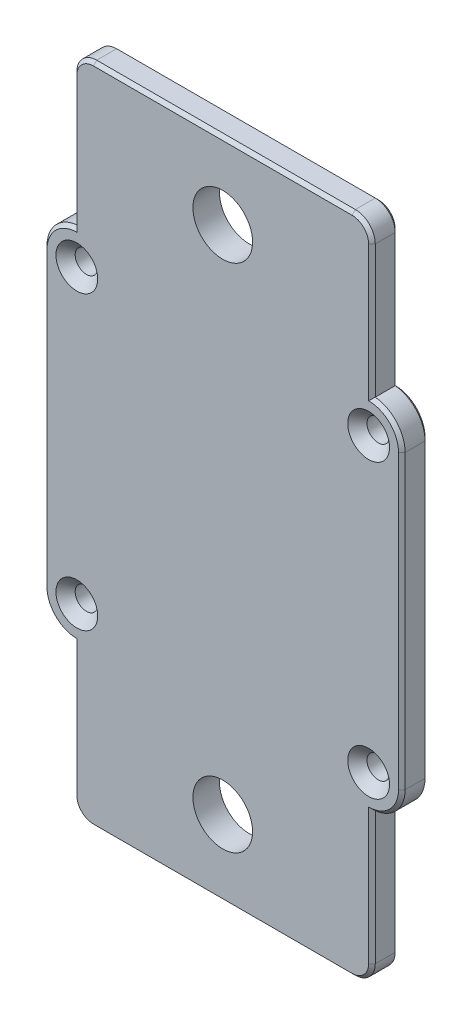
SolidWorks part; units mm, degrees
ref_plane "Plan de face" through (0, 0, 0) normal (0, 0, 1) x (1, 0, 0)
ref_plane "Plan de dessus" through (0, 0, 0) normal (0, 1, 0) x (1, 0, 0)
ref_plane "Plan de droite" through (0, 0, 0) normal (1, 0, 0) x (0, 0, -1)
sketch "Esquisse1" plane through (0, 0, 0) normal (0, 0, 1) x (1, 0, 0)
  line L0 (0, 77) -> (4.5, 77)
  line L1 (-49.5, 77) -> (-45, 77)
  line L2 (-49.5, 77) -> (-49.5, 23)
  line L3 (-49.5, 23) -> (-45, 23)
  line L4 (4.5, 77) -> (4.5, 23)
  line L5 (-45, 100) -> (0, 100)
  line L6 (-45, 100) -> (-45, 77)
  line L7 (-45, 0) -> (0, 0)
  line L8 (0, 100) -> (0, 77)
  line L9 (-45, 77) -> (0, 77) construction
  line L10 (0, 23) -> (4.5, 23)
  line L11 (-45, 23) -> (0, 23) construction
  line L12 (-45, 23) -> (-45, 0)
  line L13 (-45, 77) -> (-45, 23) construction
  line L14 (0, 23) -> (0, 0)
  line L15 (0, 77) -> (0, 23) construction
  point P12 (0, 0)
  point P13 (0, 0)
  dimension "D1" = 54
  dimension "D2" = 54
  dimension "D3" = 100
  dimension "45mm" = 45
  dimension "D4" = 23
  dimension "D5" = 4.5
extrude "Boss.-Extru.1" add sketch "Esquisse1" along normal blind 4
hole_wizard "Fraisage pour vis à tête fraisée M31" positions "Esquisse2" profile "Esquisse3" countersink size "M3" standard "Ansi Metric" end condition through all
sketch "Esquisse2" plane through (0, 0, 4) normal (0, 0, 1) x (1, 0, 0)
  line L0 (-49.5, 77) -> (-49.5, 23) construction
  line L1 (-45, 77) -> (-49.5, 77) construction
  line L2 (4.5, 23) -> (4.5, 77) construction
  line L3 (-49.5, 23) -> (-45, 23) construction
  point P0 (-44.5, 72)
  point P2 (-0.5, 72)
  point P4 (-0.5, 28)
  point P6 (-44.5, 28)
  point P13 (-21.4051, 42.7627)
  point P18 (0, 0)
  point P19 (0, 0)
  point P20 (0, 0)
  dimension "D1" = 44
  dimension "D2" = 44
  dimension "D3" = 44
  dimension "D4" = 5
  dimension "D5" = 5
  dimension "D6" = 5
  dimension "D7" = 5
  dimension "D8" = 5
sketch "Esquisse3" plane through (-44.5, 72, 4) normal (1, 0, 0) x (0, -1, 0)
  line L0 (0, 0) -> (0, 4)
  line L1 (0, 4) -> (1.7, 4)
  line L2 (1.7, 4) -> (1.7, 1.45)
  line L3 (1.7, 1.45) -> (3.15, 0)
  line L5 (3.15, 0) -> (0, 0)
  line L6 (-1.7, 1.45) -> (-3.15, 0) construction
  line L11 (0, -6.35) -> (0, 107.95) construction
  dimension "Diamètre du perçage jusqu'au prochain" = 3.4
  dimension "Profondeur du perçage jusqu'au prochain" = 4
  dimension "Diamètre du fraisage entrant" = 6.3
  dimension "Angle du fraisage entrant" = 90
fillet "Congé1" radius 5 4 edges at (-49.5, 23, 2) (-49.5, 77, 2) (4.5, 77, 2) (4.5, 23, 2)
hole_wizard "Dégagement M81" positions "Esquisse4" profile "Esquisse5" hole size "M8" standard "Ansi Metric" end condition through all
sketch "Esquisse4" plane through (0, 0, 4) normal (0, 0, 1) x (1, 0, 0)
  line L0 (0, 100) -> (-45, 100) construction
  line L2 (-45, 100) -> (-45, 77) construction
  line L3 (-45, 23) -> (-45, 0) construction
  point P0 (-22.5, 88.5)
  point P2 (-22.5, 11.5)
  point P10 (0, 0)
  point P12 (-22.5, 100)
  point P15 (-45, 88.5)
  point P16 (0, 0)
  point P19 (-45, 11.5)
sketch "Esquisse5" plane through (-22.5, 88.5, 4) normal (1, 0, 0) x (0, -1, 0)
  line L0 (0, 0) -> (0, 4)
  line L1 (0, 4) -> (4.5, 4)
  line L2 (4.5, 4) -> (4.5, 0)
  line L5 (4.5, 0) -> (0, 0)
  line L11 (0, -6.35) -> (0, 107.95) construction
  dimension "Diamètre du perçage jusqu'au prochain" = 9
  dimension "Profondeur du perçage jusqu'au prochain" = 4
fillet "Congé2" radius 3 4 edges at (0, 0, 2) (-45, 0, 2) (-45, 100, 2) (0, 100, 2)
chamfer "Chanfrein1" distance 0.5 angle 45 19 edges at (3.2081, 24.6208, 0) (4.5, 50, 0) (3.2081, 75.3792, 0) (0, 87, 0) (-0.8787, 99.1213, 0) (-22.5, 100, 0) (-44.1213, 99.1213, 0) (-45, 87, 0) (-48.2081, 75.3792, 0) (-49.5, 50, 0) (-48.2081, 24.6208, 0) (-45, 13, 0) (-44.1213, 0.8787, 0) (-22.5, 0, 0) (-0.8787, 0.8787, 0) (0, 13, 0) (3.2081, 24.6208, 4) (3.2081, 75.3792, 4) (4.5, 50, 4)
chamfer "Chanfrein2" distance 0.5 angle 45 13 edges at (0, 86.7486, 4) (-0.8787, 99.1213, 4) (-22.5, 100, 4) (-44.1213, 99.1213, 4) (-45, 87, 4) (-45, 13, 4) (-44.1213, 0.8787, 4) (-22.5, 0, 4) (-0.8787, 0.8787, 4) (0, 13.2514, 4) (-48.2081, 75.3792, 4) (-48.2081, 24.6208, 4) (-49.5, 50, 4)
